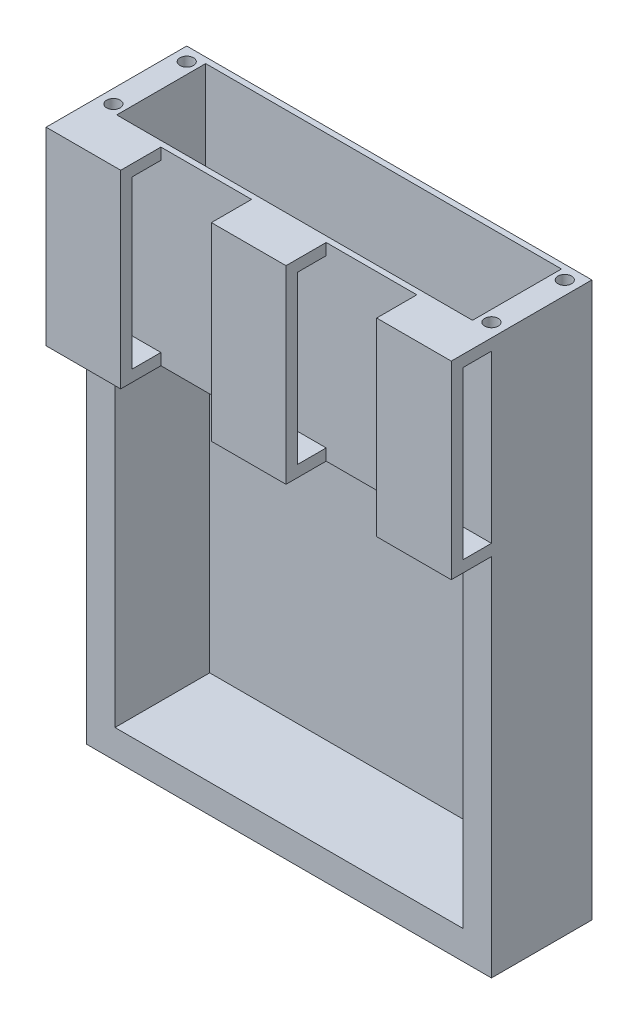
SolidWorks part; units mm, degrees
ref_plane "Front Plane" through (0, 0, 0) normal (0, 0, 1) x (1, 0, 0)
ref_plane "Top Plane" through (0, 0, 0) normal (0, 1, 0) x (1, 0, 0)
ref_plane "Right Plane" through (0, 0, 0) normal (1, 0, 0) x (0, 0, -1)
sketch "Sketch1" plane through (0, 0, 0) normal (0, 1, 0) x (1, 0, 0)
  line L1 (0, 0) -> (89.662, 0)
  line L2 (0, 0) -> (0, 22.225)
  line L3 (0, 22.225) -> (89.662, 22.225)
  line L4 (89.662, 0) -> (89.662, 22.225)
  dimension "D1" = 89.662
  dimension "D2" = 22.225
extrude "Boss-Extrude1" add sketch "Sketch1" along normal blind 87.122
sketch "Sketch2" plane through (0, 0, 0) normal (0, 0, 1) x (1, 0, 0)
  line L0 (0, 87.122) -> (0, 0) construction
  line L1 (6.35, 6.35) -> (83.312, 6.35)
  line L2 (6.35, 6.35) -> (6.35, 80.772)
  line L3 (6.35, 80.772) -> (83.312, 80.772)
  line L4 (83.312, 6.35) -> (83.312, 80.772)
  line L5 (89.662, 87.122) -> (89.662, 0) construction
  line L6 (0, 0) -> (89.662, 0) construction
  line L7 (0, 87.122) -> (89.662, 87.122) construction
  dimension "D1" = 6.35
  dimension "D2" = 6.35
  dimension "D3" = 6.35
  dimension "D4" = 6.35
extrude "Cut-Extrude1" cut sketch "Sketch2" against normal blind 20.955
sketch "Sketch4" plane through (0, 87.122, 0) normal (0, 1, 0) x (1, 0, 0)
  line L1 (0, 0) -> (89.662, 0)
  line L2 (0, 0) -> (0, 22.225)
  line L3 (0, 22.225) -> (89.662, 22.225)
  line L4 (89.662, 0) -> (89.662, 22.225)
  line L5 (5.461, 1.27) -> (84.201, 1.27)
  line L6 (5.461, 1.27) -> (5.461, 20.955)
  line L7 (5.461, 20.955) -> (84.201, 20.955)
  line L8 (84.201, 1.27) -> (84.201, 20.955)
  dimension "D1" = 5.461
  dimension "D2" = 1.27
  dimension "D3" = 5.461
  dimension "D4" = 1.27
extrude "Boss-Extrude2" add sketch "Sketch4" along normal blind 35.56
sketch "Sketch5" plane through (0, 88.392, -1.27) normal (0, 0, -1) x (1, 0, 0)
  line L0 (0, -34.29) -> (89.662, -34.29) construction
  line L3 (5.461, -34.29) -> (5.461, 1.27) construction
  circle A0 centre (18.161, -26.0274) radius 3.175
  circle A1 centre (18.161, -26.0274) radius 1.5
  circle A2 centre (18.161, -5.7074) radius 3.175
  circle A3 centre (18.161, -5.7074) radius 1.5
  circle A4 centre (52.451, -5.7074) radius 3.175
  circle A5 centre (52.451, -5.7074) radius 1.5
  circle A6 centre (52.451, -26.0274) radius 3.175
  circle A7 centre (52.451, -26.0274) radius 1.5
  dimension "D4" = 6.35
  dimension "D5" = 6.35
  dimension "D6" = 6.35
  dimension "D7" = 6.35
  dimension "D8" = 3
  dimension "D9" = 3
  dimension "D10" = 3
  dimension "D11" = 3
  dimension "D1" = 20.32
  dimension "D2" = 8.2626
  dimension "D3" = 34.29
  dimension "D12" = 12.7
extrude "Boss-Extrude5" add sketch "Sketch5" along normal blind 1.27
sketch "Sketch6" plane through (0, 122.682, 0) normal (0, 1, 0) x (1, 0, 0)
  line L0 (0, 0) -> (89.662, 0) construction
  line L1 (89.662, 22.225) -> (0, 22.225) construction
  line L2 (89.662, 0) -> (89.662, 22.225) construction
  line L3 (0, 22.225) -> (0, 0) construction
  circle A0 centre (3, 3) radius 1.5
  circle A1 centre (3, 19.225) radius 1.5
  circle A2 centre (86.662, 19.225) radius 1.5
  circle A3 centre (86.662, 3) radius 1.5
  dimension "D1" = 3
  dimension "D2" = 3
  dimension "D3" = 3
  dimension "D4" = 3
  dimension "D5" = 3
  dimension "D6" = 3
  dimension "D7" = 3
  dimension "D8" = 3
extrude "Cut-Extrude4" cut sketch "Sketch6" against normal blind 19.05
sketch "Sketch10" plane through (0, 0, 0) normal (0, 0, 1) x (1, 0, 0)
  line L0 (0, 122.682) -> (89.662, 122.682) construction
  line L1 (0, 122.682) -> (16.51, 122.682)
  line L2 (0, 122.682) -> (0, 80.772)
  line L3 (0, 80.772) -> (16.51, 80.772)
  line L4 (16.51, 122.682) -> (16.51, 80.772)
  line L5 (89.662, 122.682) -> (73.152, 122.682)
  line L6 (89.662, 122.682) -> (89.662, 80.772)
  line L7 (89.662, 80.772) -> (73.152, 80.772)
  line L8 (73.152, 122.682) -> (73.152, 80.772)
  line L9 (36.576, 122.682) -> (53.086, 122.682)
  line L10 (36.576, 122.682) -> (36.576, 80.772)
  line L11 (36.576, 80.772) -> (53.086, 80.772)
  line L12 (53.086, 122.682) -> (53.086, 80.772)
  dimension "D1" = 16.51
  dimension "D2" = 16.51
  dimension "D3" = 16.51
  dimension "D4" = 20.066
  dimension "D5" = 41.91
extrude "Boss-Extrude4" add sketch "Sketch10" along normal blind 8.89
sketch "Sketch11" plane through (0, 0, 0) normal (-1, 0, 0) x (0, 0, 1)
  line L0 (8.89, 122.682) -> (8.89, 80.772) construction
  line L1 (6.35, 120.142) -> (0, 120.142)
  line L2 (6.35, 120.142) -> (6.35, 83.312)
  line L3 (6.35, 83.312) -> (0, 83.312)
  line L4 (0, 120.142) -> (0, 83.312)
  line L5 (8.89, 80.772) -> (0, 80.772) construction
  line L6 (-22.225, 122.682) -> (8.89, 122.682) construction
  line L7 (0, 80.772) -> (0, 0) construction
  dimension "D1" = 2.54
  dimension "D2" = 2.54
  dimension "D3" = 2.54
extrude "Cut-Extrude8" cut sketch "Sketch11" against normal through all
